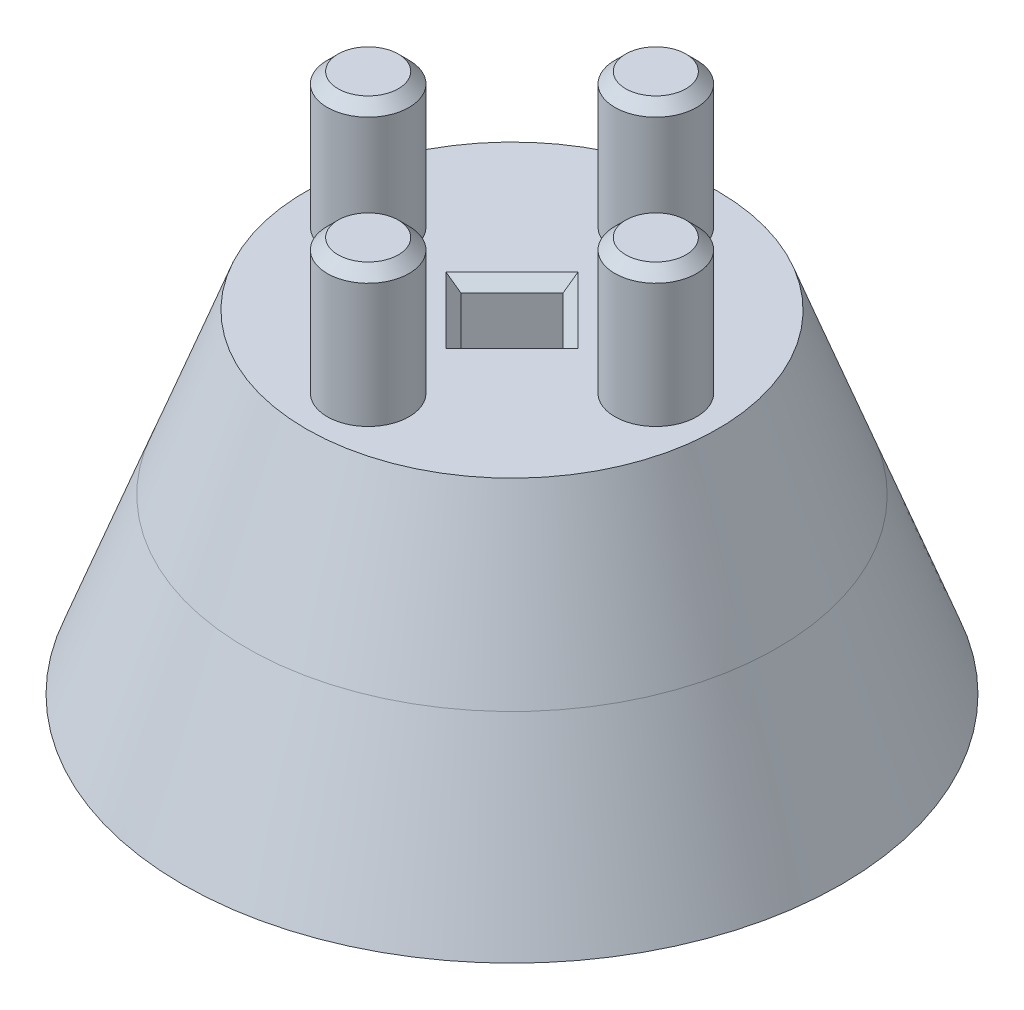
SolidWorks part; units mm, degrees
ref_plane "Front Plane" through (0, 0, 0) normal (0, 0, 1) x (1, 0, 0)
ref_plane "Top Plane" through (0, 0, 0) normal (0, 1, 0) x (1, 0, 0)
ref_plane "Right Plane" through (0, 0, 0) normal (1, 0, 0) x (0, 0, -1)
sketch "Sketch1" plane through (0, 0, 0) normal (1, 0, 0) x (0, 0, -1)
  line L0 (0, 0) -> (0, 19.5)
  line L1 (0, 19.5) -> (11.45, 19.5)
  line L2 (11.45, 19.5) -> (18.7, 0)
  line L3 (18.7, 0) -> (0, 0)
  line L4 (0, 0) -> (0, 28.4849) construction
  dimension "D1" = 37.4
  dimension "D2" = 19.5
  dimension "D3" = 22.9
revolve "Revolve1" add sketch "Sketch1" angle 360 about L4
sketch "Sketch2" plane through (0, 0, 0) normal (0, -1, 0) x (1, 0, 0)
  line L0 (-13.0767, 5) -> (13.0767, 5)
  line L1 (-13.4164, 4) -> (13.4164, 4)
  line L2 (0, 0) -> (-27.0507, 0) construction
  line L3 (-13.0767, -5) -> (13.0767, -5)
  line L4 (-13.4164, -4) -> (13.4164, -4)
  line L5 (0, 0) -> (0, 20.2875) construction
  line L6 (5, 13.0767) -> (5, -13.0767)
  line L7 (4, 13.4164) -> (4, -13.4164)
  line L8 (-5, 13.0767) -> (-5, -13.0767)
  line L9 (-4, 13.4164) -> (-4, -13.4164)
  circle A0 centre (0, 0) radius 15
  circle A1 centre (0, 0) radius 14
  dimension "D1" = 30
  dimension "D2" = 1
  dimension "D3" = 1
  dimension "D4" = 5
extrude "Cut-Extrude1" cut sketch "Sketch2" against normal blind 0.8 contours L8 A1 L0 | L7 A1 L9 L0 | L0 A1 L6 | L4 A1 L1 L6 | L1 L9 L4 L7 | L1 A1 L4 L8 | L3 A1 L8 | L9 A1 L7 L3 | L6 A1 L3 region at (-8.0694, 0, 8.0694) region at (-9.4053, 0, 0) region at (0, 0, 9.4053) region at (0, 0, 0) region at (-8.0694, 0, -8.0694) region at (8.0694, 0, 8.0694) region at (9.4053, 0, 0) region at (0, 0, -9.4053) region at (8.0694, 0, -8.0694)
sketch "Sketch3" plane through (0, 0, 0) normal (0, -1, 0) x (1, 0, 0)
  circle A0 centre (0, 0) radius 15
  circle A1 centre (0, 0) radius 21.299
  dimension "D1" = 30
extrude "Cut-Extrude2" cut sketch "Sketch3" against normal blind 1
sketch "Sketch4" plane through (0, 0.8, 0) normal (0, -1, 0) x (1, 0, 0)
  line L0 (-4, -5) -> (-4, -13.4164) construction
  line L1 (4, -13.4164) -> (4, -5) construction
  line L2 (-5, 5) -> (-5, 13.0767)
  line L3 (-13.0767, 5) -> (-5, 5)
  line L4 (-5, 5) -> (-5, 13.0767)
  line L5 (-13.0767, 5) -> (-5, 5)
  line L6 (5, 5) -> (13.0767, 5)
  line L7 (5, 13.0767) -> (5, 5)
  line L8 (5, 5) -> (13.0767, 5)
  line L9 (5, 13.0767) -> (5, 5)
  line L10 (-5, -5) -> (-13.0767, -5)
  line L11 (-5, -13.0767) -> (-5, -5)
  line L12 (-5, -5) -> (-13.0767, -5)
  line L13 (-5, -13.0767) -> (-5, -5)
  line L14 (5, -5) -> (5, -13.0767)
  line L15 (13.0767, -5) -> (5, -5)
  line L16 (5, -5) -> (5, -13.0767)
  line L17 (13.0767, -5) -> (5, -5)
  line L18 (4, -5) -> (-4, -5) construction
  line L19 (4, 5) -> (4, 13.4164)
  line L20 (-4, 13.4164) -> (-4, 5)
  line L21 (-4, 5) -> (4, 5)
  line L22 (4, 5) -> (4, 13.4164)
  line L23 (-4, 13.4164) -> (-4, 5)
  line L24 (-4, 5) -> (4, 5)
  line L25 (-5, 4) -> (-13.4164, 4)
  line L26 (-13.4164, -4) -> (-5, -4)
  line L27 (-5, -4) -> (-5, 4)
  line L28 (-5, 4) -> (-13.4164, 4)
  line L29 (-13.4164, -4) -> (-5, -4)
  line L30 (-5, -4) -> (-5, 4)
  line L31 (5, -4) -> (13.4164, -4) construction
  line L32 (4, 4) -> (-4, 4)
  line L33 (-4, 4) -> (-4, -4)
  line L34 (-4, -4) -> (4, -4)
  line L35 (4, -4) -> (4, 4)
  line L36 (4, 4) -> (-4, 4)
  line L37 (-4, 4) -> (-4, -4)
  line L38 (-4, -4) -> (4, -4)
  line L39 (4, -4) -> (4, 4)
  line L40 (13.4164, 4) -> (5, 4) construction
  line L41 (5, 4) -> (5, -4) construction
  line L42 (-4, -5) -> (-4, -13.4164)
  line L43 (4, -13.4164) -> (4, -5)
  line L44 (4, -5) -> (-4, -5)
  line L45 (5, -4) -> (13.4164, -4)
  line L46 (13.4164, 4) -> (5, 4)
  line L47 (5, 4) -> (5, -4)
  line L48 (0, 0) -> (0, 14) construction
  line L49 (14, 0) -> (-14, 0) construction
  line L50 (0, -14) -> (0, 0) construction
  line L51 (4.2426, 0) -> (0, 4.2426)
  line L52 (2.8284, 0) -> (0, 2.8284)
  line L53 (0, 2.8284) -> (-2.8284, 0)
  line L54 (-2.8284, 0) -> (0, -2.8284)
  line L55 (0, -2.8284) -> (2.8284, 0)
  line L56 (0, 4.2426) -> (-4.2426, 0)
  line L57 (-4.2426, 0) -> (0, -4.2426)
  line L58 (0, -4.2426) -> (4.2426, 0)
  line L59 (-13.9911, 0.5) -> (13.9911, 0.5)
  line L60 (-13.9911, -0.5) -> (13.9911, -0.5)
  line L61 (-0.5, 13.9911) -> (-0.5, -13.9911)
  line L62 (0.5, 13.9911) -> (0.5, -13.9911)
  line L63 (0, 10) -> (30.8306, 10) construction
  line L64 (-4, 10.5) -> (4, 10.5)
  line L65 (-4, 9.5) -> (4, 9.5)
  line L66 (9.5, 4) -> (9.5, -4)
  line L67 (10.5, 4) -> (10.5, -4)
  line L68 (4, -9.5) -> (-4, -9.5)
  line L69 (4, -10.5) -> (-4, -10.5)
  line L70 (-9.5, -4) -> (-9.5, 4)
  line L71 (-10.5, -4) -> (-10.5, 4)
  arc A0 (-4, -13.4164) -> (4, -13.4164) centre (0, 0) ccw construction
  arc A1 (-5, 13.0767) -> (-13.0767, 5) centre (0, 0) ccw
  arc A2 (-5, 13.0767) -> (-13.0767, 5) centre (0, 0) ccw
  arc A3 (13.0767, 5) -> (5, 13.0767) centre (0, 0) ccw
  arc A4 (13.0767, 5) -> (5, 13.0767) centre (0, 0) ccw
  arc A5 (-13.0767, -5) -> (-5, -13.0767) centre (0, 0) ccw
  arc A6 (-13.0767, -5) -> (-5, -13.0767) centre (0, 0) ccw
  arc A7 (5, -13.0767) -> (13.0767, -5) centre (0, 0) ccw
  arc A8 (5, -13.0767) -> (13.0767, -5) centre (0, 0) ccw
  arc A9 (4, 13.4164) -> (-4, 13.4164) centre (0, 0) ccw
  arc A10 (4, 13.4164) -> (-4, 13.4164) centre (0, 0) ccw
  arc A11 (-13.4164, 4) -> (-13.4164, -4) centre (0, 0) ccw
  arc A12 (-13.4164, 4) -> (-13.4164, -4) centre (0, 0) ccw
  arc A13 (13.4164, -4) -> (13.4164, 4) centre (0, 0) ccw construction
  arc A14 (-4, -13.4164) -> (4, -13.4164) centre (0, 0) ccw
  arc A15 (13.4164, -4) -> (13.4164, 4) centre (0, 0) ccw
  circle A16 centre (-10, 0) radius 2.6
  circle A17 centre (0, 10) radius 2.6
  circle A18 centre (10, 0) radius 2.6
  circle A19 centre (0, -10) radius 2.6
  circle A20 centre (0, 0) radius 2 construction
  circle A21 centre (0, 10) radius 3.6
  circle A22 centre (-10, 0) radius 3.6
  circle A23 centre (0, -10) radius 3.6
  circle A24 centre (10, 0) radius 3.6
  point P82 (-4.2426, -3.7321)
  point P83 (0, 0)
  point P97 (0, 0)
  dimension "D8" = 5.2
  dimension "D9" = 10
  dimension "D10" = 10
  dimension "D11" = 10
  dimension "D12" = 10
  dimension "D13" = 4
  dimension "D17" = 0.5
  dimension "D18" = 1
  dimension "D19" = 0.5
  dimension "D1" = 0
  dimension "D2" = 0
  dimension "D3" = 0
  dimension "D4" = 0
  dimension "D5" = 0
  dimension "D6" = 0
  dimension "D7" = 0
  dimension "D14" = 1
  dimension "D15" = 1
  dimension "D16" = 1
  dimension "D20" = 4
extrude "Cut-Extrude3" cut sketch "Sketch4" against normal blind 3.7 contours A21 L65 L23 L24 L61 | A21 L61 A10 L23 L64 | A21 L64 L22 A10 L62 | A21 L62 L24 L22 L65 | L8 A4 L9 | A22 L59 L30 L28 L70 | A22 L70 L29 L30 L60 | A22 L60 A12 L29 L71 | A22 L71 L28 A12 L59 | L61 L36 L37 L59 L56 | L61 L57 L60 L37 L38 | L58 L62 L38 L39 L60 | L36 L62 L51 L59 L39 | A24 L66 L46 L47 L59 | A24 L60 L47 L45 L66 | A24 L67 L45 A15 L60 | A24 L59 A15 L46 L67 | L16 A8 L17 | A23 L68 L43 L44 L62 | A23 L61 L44 L42 L68 | A23 L69 L42 A14 L61 | A23 L62 A14 L43 L69 | L12 A6 L13 | L4 A2 L5 region at (8.0694, 0.8, 8.0694) region at (-8.0694, 0.8, -8.0694) region at (8.0694, 0.8, -8.0694) region at (2.6365, 0.8, 6.4797) region at (2.8661, 0.8, 12.7307) region at (-2.6365, 0.8, 6.4797) region at (2.7531, 0.8, 2.7531) region at (-2.7531, 0.8, 2.7531) region at (-2.8661, 0.8, 12.7307) region at (6.4797, 0.8, 2.6365) region at (-6.4797, 0.8, 2.6365) region at (6.4797, 0.8, -2.6365) region at (-6.4797, 0.8, -2.6365) region at (2.7531, 0.8, -2.7531) region at (-2.7531, 0.8, -2.7531) region at (12.7307, 0.8, 2.8661) region at (-12.7307, 0.8, 2.8661) region at (12.7307, 0.8, -2.8661) region at (-12.7307, 0.8, -2.8661) region at (2.6365, 0.8, -6.4797) region at (-2.6365, 0.8, -6.4797) region at (2.8661, 0.8, -12.7307) region at (-2.8661, 0.8, -12.7307)
extrude "Cut-Extrude4" cut sketch "Sketch4<3>" against normal blind 8.3 contours L65 A17 L61 | L64 A17 L65 L61 | L61 A17 L64 | L62 A17 L61 L64 | L64 A17 L62 | L65 A17 L64 L62 | L61 L65 L62 L64 | L61 A17 L62 L65 | L62 A17 L65 | L59 A18 L67 | L67 A18 L66 L59 | L66 A18 L59 | L59 A18 L60 L66 | L60 A18 L66 | L66 A18 L67 L60 | L67 A18 L60 | L67 L59 L66 L60 | L60 A18 L59 L67 | A19 | A16 | L53 L54 L55 L52 region at (1.3208, 0.8, 8.6792) region at (1.542, 0.8, 10) region at (0, 0.8, 8.458) region at (1.3208, 0.8, 11.3208) region at (0, 0.8, 10) region at (-1.3208, 0.8, 8.6792) region at (0, 0.8, 11.542) region at (-1.542, 0.8, 10) region at (-1.3208, 0.8, 11.3208) region at (8.6792, 0.8, 1.3208) region at (8.458, 0.8, 0) region at (8.6792, 0.8, -1.3208) region at (10, 0.8, 1.542) region at (10, 0.8, 0) region at (10, 0.8, -1.542) region at (11.3208, 0.8, 1.3208) region at (11.542, 0.8, 0) region at (11.3208, 0.8, -1.3208)
sketch "Sketch4<3>" plane through (0, 0.8, 0) normal (0, -1, 0) x (1, 0, 0) same geometry as "Sketch4"
sketch "Sketch6" plane through (0, 9.1, 0) normal (0, -1, 0) x (1, 0, 0)
  line L4 (2.8284, 0) -> (0, 2.8284)
  line L5 (0, 2.8284) -> (-2.8284, 0)
  line L6 (-2.8284, 0) -> (0, -2.8284)
  line L7 (0, -2.8284) -> (2.8284, 0)
  line L8 (2.8284, 0) -> (0, 2.8284)
  line L9 (0, 2.8284) -> (-2.8284, 0)
  line L10 (-2.8284, 0) -> (0, -2.8284)
  line L11 (0, -2.8284) -> (2.8284, 0)
  dimension "D1" = 0
extrude "Cut-Extrude5" cut sketch "Sketch6" against normal through all
sketch "Sketch7" plane through (0, 9.1, 0) normal (0, -1, 0) x (1, 0, 0)
  circle A8 centre (10, 0) radius 3.6
  circle A9 centre (10, 0) radius 3.6
  circle A11 centre (0, 10) radius 3.6
  circle A12 centre (0, 10) radius 3.6
  circle A14 centre (-10, 0) radius 3.6
  circle A15 centre (-10, 0) radius 3.6
  circle A17 centre (0, -10) radius 3.6
  circle A18 centre (0, -10) radius 3.6
  dimension "D1" = 1
  dimension "D2" = 1
  dimension "D3" = 1
  dimension "D4" = 1
extrude "Cut-Extrude6" cut sketch "Sketch7" against normal blind 1.5
ref_plane "Plane1" through (0, 10.6, 0) normal (0, -1, 0) x (-1, 0, 0)
split "Split1" trim tools "Plane1" bodies to split 107 resulting bodies 108 109
sketch "Sketch8" plane through (0, 19.5, 0) normal (0, 1, 0) x (1, 0, 0)
  line L0 (0, 8) -> (0, -8) construction
  line L1 (8, 0) -> (-8, 0) construction
  circle A0 centre (0, 0) radius 8 construction
  circle A1 centre (0, 8) radius 2.275
  circle A2 centre (-8, 0) radius 2.275
  circle A3 centre (8, 0) radius 2.275
  circle A4 centre (0, -8) radius 2.275
  dimension "D1" = 16
  dimension "D2" = 4.55
extrude "Boss-Extrude1" add sketch "Sketch8" along normal blind 7.5
chamfer "Chamfer1" distance 0.6 angle 45 12 edges at (0, 27, 10.275) (8, 27, 2.275) (0, 27, -5.725) (-1.4142, 10.6, 1.4142) (1.4142, 10.6, 1.4142) (1.4142, 10.6, -1.4142) (-1.4142, 10.6, -1.4142) (1.4142, 19.5, 1.4142) (-1.4142, 19.5, 1.4142) (1.4142, 19.5, -1.4142) (-1.4142, 19.5, -1.4142) (-8, 27, 2.275)
sketch "Sketch9" plane through (0, 9.1, 0) normal (0, 1, 0) x (1, 0, 0)
  circle A0 centre (0, -10) radius 2.6 construction
  circle A1 centre (-10, 0) radius 2.6 construction
  circle A2 centre (0, 10) radius 2.6 construction
  circle A3 centre (10, 0) radius 2.6 construction
  circle A4 centre (0, -10) radius 2.6
  circle A5 centre (-10, 0) radius 2.6
  circle A6 centre (0, 10) radius 2.6
  circle A7 centre (10, 0) radius 2.6
extrude "Boss-Extrude2" add sketch "Sketch9" against normal blind 0.2
chamfer "Chamfer2" distance 0.6 angle 45 4 edges at (1.4142, 10.6, 1.4142) (-1.4142, 10.6, 1.4142) (-1.4142, 10.6, -1.4142) (1.4142, 10.6, -1.4142)
fillet "Fillet1" radius 0.3 12 edges at (5, 2.25, -13.0767) (5, 2.25, -5) (13.0767, 2.25, -5) (-13.0767, 2.25, -5) (-5, 2.25, -13.0767) (-13.0767, 2.25, 5) (-5, 2.25, 13.0767) (-5, 2.25, -5) (-5, 2.25, 5) (13.0767, 2.25, 5) (5, 2.25, 5) (5, 2.25, 13.0767)
fillet "Fillet2" radius 0.3 30 edges at (-4, 2.65, -9.5) (-4, 2.65, -10.5) (-0.5, 2.65, -13.9911) (0.5, 2.65, -13.9911) (4, 2.65, -9.5) (-0.5, 2.65, -6.4349) (0.5, 2.65, -6.4349) (0.5, 2.65, -5) (4, 2.65, -10.5) (-0.5, 2.65, -5) (-3.7426, 2.65, 0.5) (-3.7426, 2.65, -0.5) (-0.5, 2.65, -3.7426) (0.5, 2.65, -3.7426) (3.7426, 2.65, 0.5) (3.7426, 2.65, -0.5) (-0.5, 2.65, 3.7426) (0.5, 2.65, 3.7426) (-0.5, 2.65, 13.9911) (-4, 2.65, 10.5) (-4, 2.65, 9.5) (4, 2.65, 9.5) (4, 2.65, 10.5) (0.5, 2.65, 13.9911) (0.5, 2.65, 6.4349) (-0.5, 2.65, 6.4349) (-0.5, 2.65, 5) (0.5, 2.65, 5) (-4, 2.25, 5) (4, 2.25, 5)
fillet "Fillet3" radius 0.3 20 edges at (13.9911, 2.65, -0.5) (13.9911, 2.65, 0.5) (10.5, 2.65, 4) (9.5, 2.65, 4) (10.5, 2.65, -4) (9.5, 2.65, -4) (5, 2.65, -0.5) (6.4349, 2.65, -0.5) (6.4349, 2.65, 0.5) (5, 2.65, 0.5) (-6.4349, 2.65, 0.5) (-6.4349, 2.65, -0.5) (-5, 2.65, -0.5) (-5, 2.65, 0.5) (-9.5, 2.65, 4) (-10.5, 2.65, 4) (-13.9911, 2.65, 0.5) (-13.9911, 2.65, -0.5) (-10.5, 2.65, -4) (-9.5, 2.65, -4)
fillet "Fillet4" radius 0.3 18 edges at (9.5, 2.65, -3.5651) (10.5, 2.65, -3.5651) (13.5651, 2.65, -0.5) (13.5651, 2.65, 0.5) (9.5, 2.65, 3.5651) (10.5, 2.65, 3.5651) (3.5651, 2.65, 10.5) (3.5651, 2.65, 9.5) (-3.5651, 2.65, 9.5) (-3.5651, 2.65, 10.5) (0.5, 2.65, 13.5651) (-0.5, 2.65, 13.5651) (-10.5, 2.65, -3.5651) (-9.5, 2.65, -3.5651) (-13.5651, 2.65, -0.5) (-13.5651, 2.65, 0.5) (-9.5, 2.65, 3.5651) (-10.5, 2.65, 3.5651)
fillet "Fillet5" radius 0.3 14 edges at (0.5, 2.65, 4) (-0.5, 2.65, 4) (-4, 2.65, 0.5) (-4, 2.65, -0.5) (-0.5, 2.65, -4) (0.5, 2.65, -4) (4, 2.65, -0.5) (4, 2.65, 0.5) (-0.5, 2.65, -13.5651) (0.5, 2.65, -13.5651) (-3.5651, 2.65, -9.5) (-3.5651, 2.65, -10.5) (3.5651, 2.65, -10.5) (3.5651, 2.65, -9.5)
delete or keep bodies "Body-Delete/Keep 1" [suppressed] type keep bodies bodies 111
